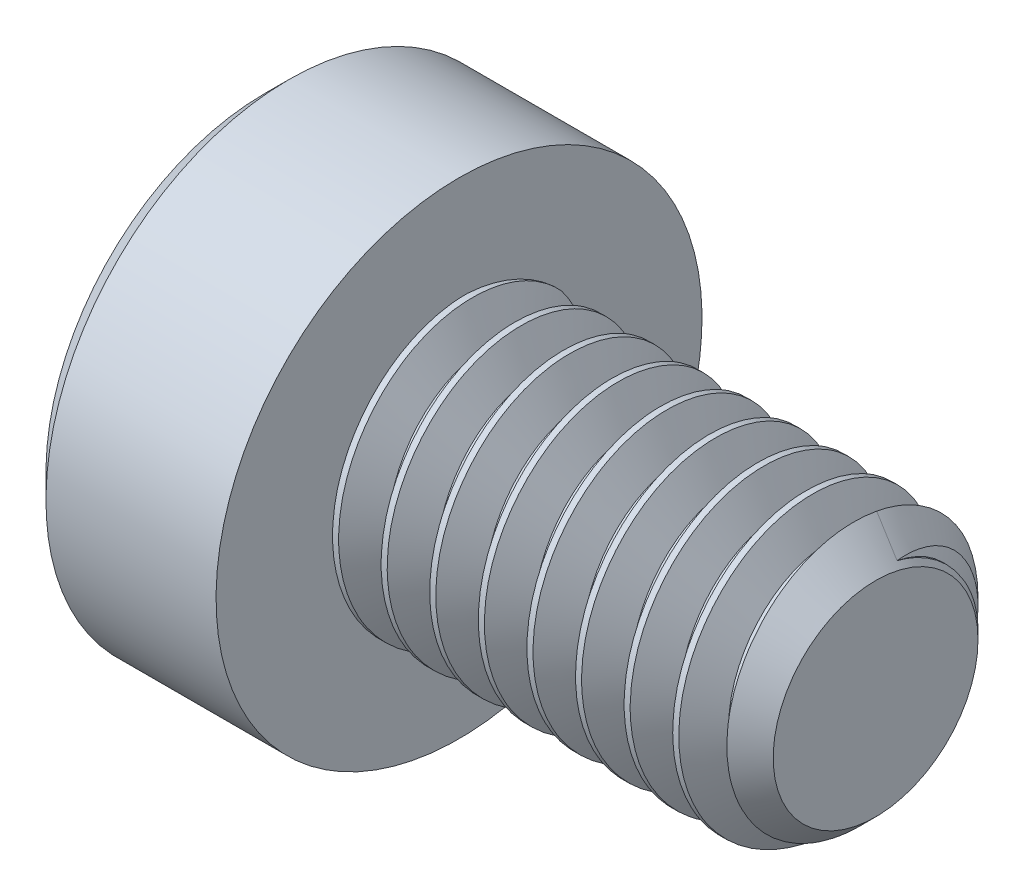
SolidWorks part; units mm, degrees
ref_plane "Front Plane" through (0, 0, 0) normal (0, 0, 1) x (1, 0, 0)
ref_plane "Top Plane" through (0, 0, 0) normal (0, 1, 0) x (1, 0, 0)
ref_plane "Right Plane" through (0, 0, 0) normal (1, 0, 0) x (0, 0, -1)
sketch "Sketch1" plane through (0, 0, 0) normal (0, 0, 1) x (1, 0, 0)
  line L0 (3, 0) -> (-3, 0) construction
  line L1 (3, 2) -> (3, -2) construction
  line L2 (-3, 3.5) -> (-3, -3.5) construction
  line L3 (-3, 3.5) -> (-5.45, 3.5) construction
  line L4 (-5.45, 3.5) -> (-5.8, 3.15) construction
  line L5 (-5.8, 3.15) -> (-5.8, -3.15) construction
  line L6 (-5.8, -3.15) -> (-5.45, -3.5) construction
  line L7 (-5.45, -3.5) -> (-3, -3.5) construction
  point P7 (-3.38, 0)
  point P12 (0.2, -2)
  dimension "D1" = 45
  dimension "Dec." = 4
  dimension "Length" = 6
  dimension "Head Dia" = 7
  dimension "Head Height" = 2.8
  dimension "Hex Depth" = 2.42
  dimension "Chamfer" = 0.35
  dimension "D2" = 2.8
ref_plane "Plane1" through (3, 0, 0) normal (1, 0, 0) x (0, 0, -1)
ref_plane "Plane2" through (-5.8, 0, 0) normal (1, 0, 0) x (0, 0, -1)
sketch "Sketch2" plane through (3, 0, 0) normal (1, 0, 0) x (0, 0, -1)
  circle A0 centre (0, 0) radius 2
extrude "Boss-Extrude1" add sketch "Sketch2" against normal up to vertex (6 mm away) up to point (-3, 0, 0)
sketch "Sketch3" plane through (3, 0, 0) normal (1, 0, 0) x (0, 0, -1)
  circle A0 centre (0, 0) radius 2 construction
  circle A1 centre (0, 0) radius 2
curve "Helix/Spiral1" pitch 0.7 height 6.7 radius 2 centre (3, 0, 0) axis (-1, 0, 0) start towards (0, 1, 0) parameters "Pitch"=0.7
chamfer "Chamfer1" distance 0.525 angle 45 1 edges at (3, 0, -2)
sketch "Sketch5" plane through (0, 0, 0) normal (0, 0, 1) x (1, 0, 0)
  line L0 (2.6938, 2) -> (3.3062, 2)
  line L1 (3.3062, 2) -> (3.0437, 1.5453)
  line L2 (3.0437, 1.5453) -> (2.9562, 1.5453)
  line L3 (2.9562, 1.5453) -> (2.6938, 2)
  line L4 (3, 1.5453) -> (3, 2) construction
  line L5 (2.825, 1.7727) -> (3.175, 1.7727) construction
  dimension "D1" = 60
  dimension "D2" = 0.35
  dimension "D3" = 0.0875
sweep "Cut-Sweep1" cut profiles "Sketch5" path "Helix/Spiral1" align with end faces yes
sketch "Sketch4" plane through (-5.8, 0, 0) normal (1, 0, 0) x (0, 0, -1)
  line L0 (-3.5, 0.7937) -> (3.5, 0.7937) construction
  line L1 (0, 1.4434) -> (-1.25, 0.7217)
  line L2 (-1.25, 0.7217) -> (-1.25, -0.7217)
  line L3 (-1.25, -0.7217) -> (0, -1.4434)
  line L4 (0, -1.4434) -> (1.25, -0.7217)
  line L5 (1.25, -0.7217) -> (1.25, 0.7217)
  line L6 (1.25, 0.7217) -> (0, 1.4434)
  line L7 (0, 0) -> (0, 0.7937) construction
  circle A0 centre (0, 0) radius 1.25 construction
  dimension "Hex Size" = 2.5
  dimension "D1" = 7
  dimension "D2" = 0.7937
sketch "Sketch6" plane through (0, 0, 0) normal (0, 0, 1) x (1, 0, 0)
  line L0 (-5.45, 3.5) -> (-5.8, 3.15) construction
  line L1 (-3, 3.5) -> (-5.45, 3.5) construction
  line L2 (-3, 3.5) -> (-3, -3.5) construction
  line L3 (-5.8, 3.15) -> (-5.8, -3.15) construction
  line L4 (-5.45, 3.5) -> (-5.8, 3.15)
  line L5 (-3, 3.5) -> (-5.45, 3.5)
  line L6 (-3, 3.5) -> (-3, 0)
  line L7 (-5.8, 3.15) -> (-5.8, 0)
  line L8 (-3, 0) -> (-5.8, 0) construction
  line L9 (-3, 0) -> (-5.8, 0)
revolve "Revolve1" add sketch "Sketch6" angle 360 about L8
extrude "Cut-Extrude1" cut sketch "Sketch4" along normal up to vertex (2.42 mm away) up to point (-3.38, 0, 0)
sketch "Sketch8" plane through (-5.8, 0, 0) normal (-1, 0, 0) x (0, 0, 1)
  circle A1 centre (0, 0) radius 1.4434
extrude "Cut-Extrude2" cut sketch "Sketch8" against normal through all draft 45
equation "\"D3@Helix/Spiral1\" = \"Length@Sketch1\"+\"Pitch@Helix/Spiral1\""
equation "\"D3@Sketch5\" = \"Pitch@Helix/Spiral1\"*.125"
equation "\"D2@Sketch5\" = \"Pitch@Helix/Spiral1\"*.50"
equation "\"D1@Chamfer1\" = \"Pitch@Helix/Spiral1\"*.75"
equation "\"D2@Sketch1\" = \"Pitch@Helix/Spiral1\"*4"
equation "\"D1@Sketch4\" = \"Head Dia@Sketch1\""
equation "\"Chamfer@Sketch1\" = \"Head Height@Sketch1\"/8"
